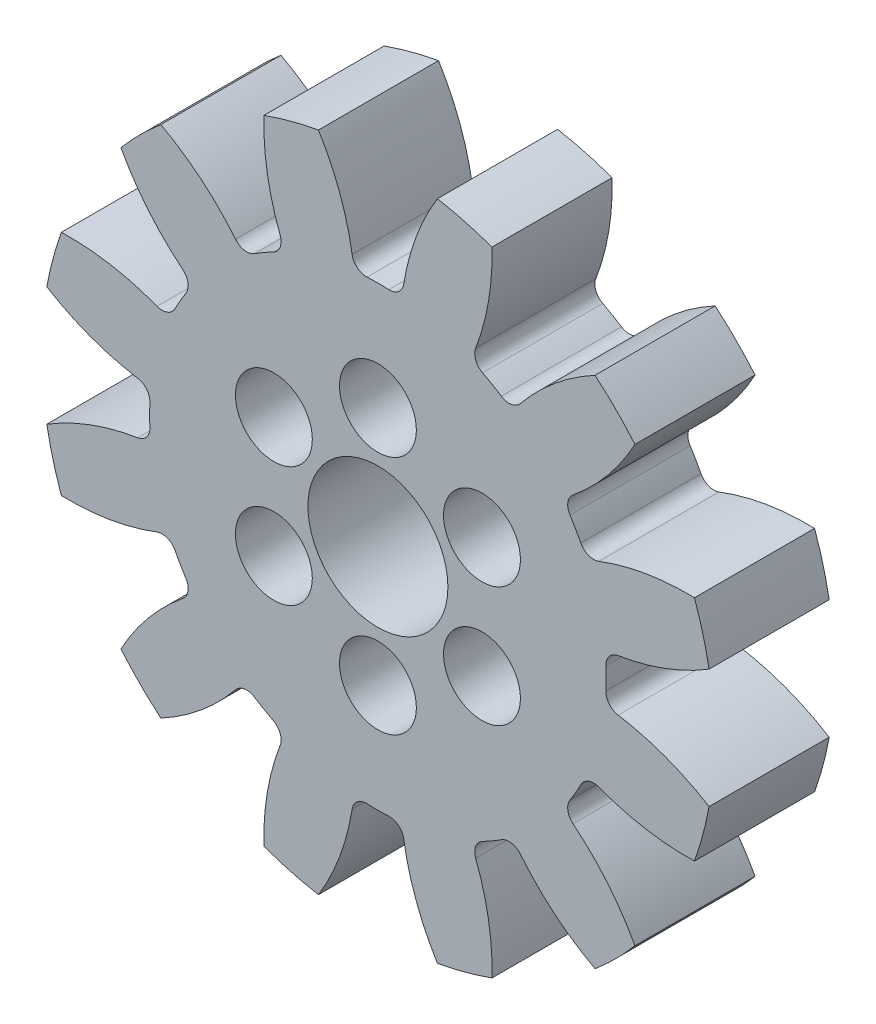
SolidWorks part; units mm, degrees
ref_plane "Front Plane" through (0, 0, 0) normal (0, 0, 1) x (1, 0, 0)
ref_plane "Top Plane" through (0, 0, 0) normal (0, 1, 0) x (1, 0, 0)
ref_plane "Right Plane" through (0, 0, 0) normal (1, 0, 0) x (0, 0, -1)
sketch "Sketch1" plane through (0, 0, 0) normal (0, 0, 1) x (1, 0, 0)
  circle A0 centre (0, 0) radius 12
  circle A1 centre (0, 0) radius 9.5
  circle A2 centre (0, 0) radius 14
  dimension "D1" = 24
  dimension "D2" = 28
  dimension "D3" = 4.5
extrude "Boss-Extrude1" add sketch "Sketch1" along normal mid plane 5 contours A2
sketch "Sketch2" plane through (0, 0, 0) normal (0, 0, 1) x (1, 0, 0)
  line L0 (0, 0) -> (0, 14) construction
  line L1 (-0.9997, 9.4472) -> (0, 0) construction
  line L2 (-1.5663, 11.8973) -> (1.5663, 11.8973) construction
  line L3 (0, 7.5939) -> (-2.7213, 15.0705) construction
  line L4 (0, 0) -> (3.6235, 13.523) construction
  line L5 (1.5663, 11.8973) -> (4.5922, 11.0866) construction
  circle A0 centre (0, 0) radius 14 construction
  arc A1 (-3.3146, 14.9512) -> (-0.9997, 9.4472) centre (-11.2897, 8.3583) cw
  arc A2 (3.3146, 14.9512) -> (0.9997, 9.4472) centre (11.2897, 8.3583) ccw
  arc A3 (3.3146, 14.9512) -> (-3.3146, 14.9512) centre (0, 0) ccw
  arc A4 (0.9997, 9.4472) -> (-0.9997, 9.4472) centre (0, 0) ccw
  circle A6 centre (0, 0) radius 9.5 construction
  circle A7 centre (0, 0) radius 12 construction
  dimension "D1" = 20
  dimension "D2" = 15
extrude "Cut-Extrude1" cut sketch "Sketch2" against normal through all both and the other way through all
fillet "Fillet1" radius 0.6 1 edges at (-0.9997, 9.4472, 0) type face fillet first side face at (-1.6166, 11.6546, 0) second side face at (0, 9.4736, 0)
fillet "Fillet2" radius 0.6 1 edges at (0.9997, 9.4472, 0) type face fillet first side face at (1.6166, 11.6546, 0) second side face at (0.2746, 9.4821, 0)
sketch "Sketch3" plane through (0, 0, 2.5) normal (0, 0, 1) x (1, 0, 0)
pattern_circular "CirPattern2" count 12 over 360 about axis through (0, 0, 2.5) along (0, 0, 1) of "Fillet1", "Cut-Extrude1", "Fillet2"
sketch "Sketch4" plane through (0, 0, 2.5) normal (0, 0, 1) x (1, 0, 0)
  line L0 (0, 0) -> (0, 8.1574) construction
  circle A0 centre (0, 0) radius 3
  circle A1 centre (0, 5) radius 1.5
  circle A2 centre (4.3301, 2.5) radius 1.5
  circle A3 centre (4.3301, -2.5) radius 1.5
  circle A4 centre (0, -5) radius 1.5
  circle A5 centre (-4.3301, -2.5) radius 1.5
  circle A6 centre (-4.3301, 2.5) radius 1.5
  point P18 (0, 0)
  dimension "D1" = 6
  dimension "D2" = 3
  dimension "D3" = 5
  dimension "D4" = 6
extrude "Cut-Extrude2" cut sketch "Sketch4" against normal through all both and the other way through all
sketch "Sketch5" plane through (0, 0, 2.5) normal (0, 0, 1) x (1, 0, 0)
  circle A0 centre (0, 5) radius 1.6
  circle A1 centre (-4.3301, -2.5) radius 1.5
  circle A2 centre (-4.3301, -2.5) radius 1.5 construction
  circle A3 centre (0, -5) radius 1.5
  circle A4 centre (0, -5) radius 1.5 construction
  circle A5 centre (4.3301, -2.5) radius 1.5
  circle A6 centre (4.3301, -2.5) radius 1.5 construction
  circle A7 centre (4.3301, 2.5) radius 1.5
  circle A8 centre (4.3301, 2.5) radius 1.5 construction
  circle A9 centre (0, 5) radius 1.5
  circle A10 centre (0, 5) radius 1.5 construction
  circle A11 centre (0, 0) radius 3
  circle A12 centre (0, 0) radius 3 construction
  circle A13 centre (-4.3301, 2.5) radius 1.5
  circle A14 centre (-4.3301, 2.5) radius 1.5 construction
  circle A15 centre (4.3301, 2.5) radius 1.6
  circle A16 centre (4.3301, -2.5) radius 1.6
  circle A17 centre (0, -5) radius 1.6
  circle A18 centre (0, 0) radius 1.6
  circle A19 centre (-4.3301, -2.5) radius 1.6
  circle A20 centre (-4.3301, 2.5) radius 1.6
  dimension "D8" = 3.2
  dimension "D1" = 0
  dimension "D2" = 0
  dimension "D3" = 0
  dimension "D4" = 0
  dimension "D5" = 0
  dimension "D6" = 0
  dimension "D7" = 0
extrude "Cut-Extrude3" cut sketch "Sketch5" against normal through all
draft "Draft1" type of draft neutral plane draft angle 1 faces to draft 1 face at (3, 0, 2.5) neutral plane through (0, 0, -2.5) neutral plane normal (0, 0, -1) parameters "D1"=1
equation "\"Number of Teeth\"= 12"
equation "\"Module\"= 2mm"
equation "\"D2@Sketch2\"=180 / \"Number of Teeth\""
equation "\"D1@Sketch1\"= \"Module\" * \"Number of Teeth\""
equation "\"D2@Sketch1\"=(\"Number of Teeth\" + 2) * \"Module\""
equation "\"D3@Sketch1\"= \"Module\" * 2.25"
equation "\"D1@CirPattern2\"= \"Number of Teeth\""
